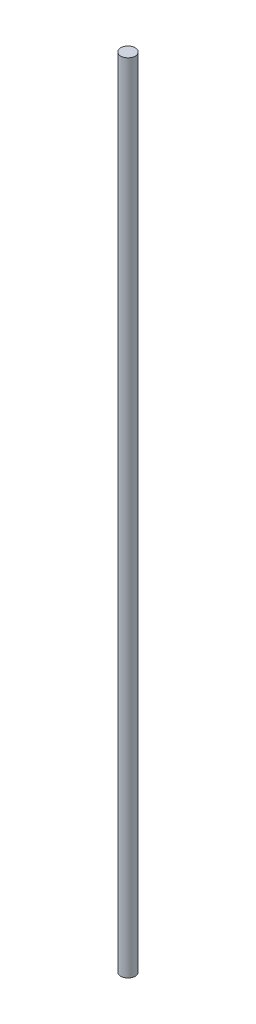
SolidWorks part; units mm, degrees
ref_plane "Front" through (0, 0, 0) normal (0, 0, 1) x (1, 0, 0)
ref_plane "Top" through (0, 0, 0) normal (0, 1, 0) x (1, 0, 0)
ref_plane "Right" through (0, 0, 0) normal (1, 0, 0) x (0, 0, -1)
sketch "Sketch1" plane through (0, 0, 0) normal (0, 1, 0) x (1, 0, 0)
  circle A0 centre (0, 0) radius 12.7
  dimension "D1" = 25.4
extrude "Boss-Extrude1" add sketch "Sketch1" along normal blind 1397
